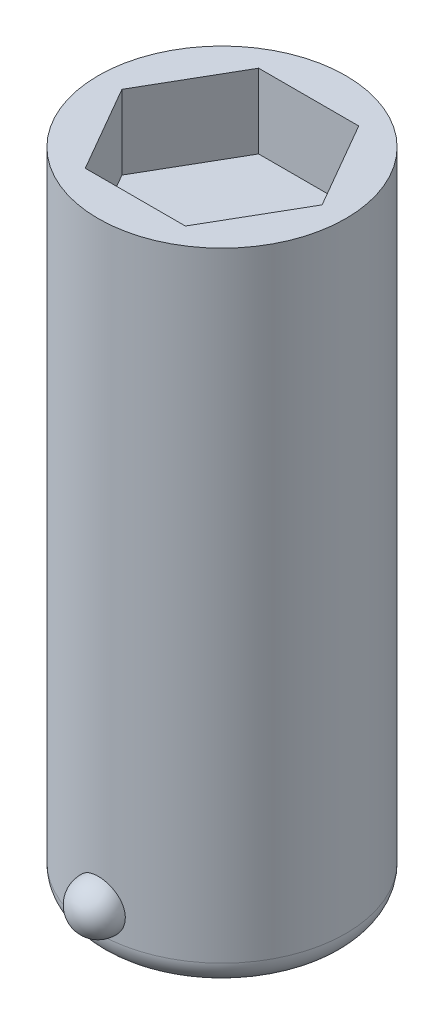
SolidWorks part; units mm, degrees
ref_plane "Front Plane" through (0, 0, 0) normal (0, 0, 1) x (1, 0, 0)
ref_plane "Top Plane" through (0, 0, 0) normal (0, 1, 0) x (1, 0, 0)
ref_plane "Right Plane" through (0, 0, 0) normal (1, 0, 0) x (0, 0, -1)
sketch "Sketch1" plane through (0, 0, 0) normal (0, 1, 0) x (1, 0, 0)
  circle A0 centre (0, 0) radius 5
  dimension "D1" = 10
extrude "Boss-Extrude1" add sketch "Sketch1" along normal blind 26
sketch "Sketch2" plane through (0, 0, 0) normal (0, 0, 1) x (1, 0, 0)
  line L0 (0, -4.1) -> (0, 4.1)
  arc A0 (0, 4.1) -> (0, -4.1) centre (0, 0) cw
  point P3 (0, 0)
  dimension "D1" = 8.2
revolve "Cut-Revolve1" cut sketch "Sketch2" angle 360 about L0
ref_plane "Plane2" through (0, 2, 0) normal (0, 1, 0) x (1, 0, 0)
sketch "Sketch4" plane through (0, 2, 0) normal (0, 1, 0) x (1, 0, 0)
  line L0 (0, 0) -> (0, 6.724) construction
  line L1 (0, 6) -> (0, 5)
  arc A0 (0.995, 4.9) -> (0, 6) centre (0, 5) ccw
  circle A1 centre (0, 0) radius 5 construction
  arc A2 (0, 5) -> (0.995, 4.9) centre (0, 0) cw
  point P10 (0, 0)
  dimension "D1" = 1
revolve "Revolve1" add sketch "Sketch4" angle 360 about L0
sketch "Sketch5" plane through (0, 26, 0) normal (0, 1, 0) x (1, 0, 0)
  line L1 (-4.0415, 0) -> (-2.0207, -3.5)
  line L2 (-2.0207, -3.5) -> (2.0207, -3.5)
  line L3 (2.0207, -3.5) -> (4.0415, 0)
  line L4 (4.0415, 0) -> (2.0207, 3.5)
  line L5 (2.0207, 3.5) -> (-2.0207, 3.5)
  line L6 (-2.0207, 3.5) -> (-4.0415, 0)
  circle A0 centre (0, 0) radius 3.5 construction
  dimension "D1" = 7
extrude "Cut-Extrude1" cut sketch "Sketch5" against normal blind 3
mirror "Mirror1" about plane through (0, 0, 0) normal (0, 0, 1) of "Revolve1"
fillet "Fillet1" radius 1 1 edges at (0, 0, 5)
